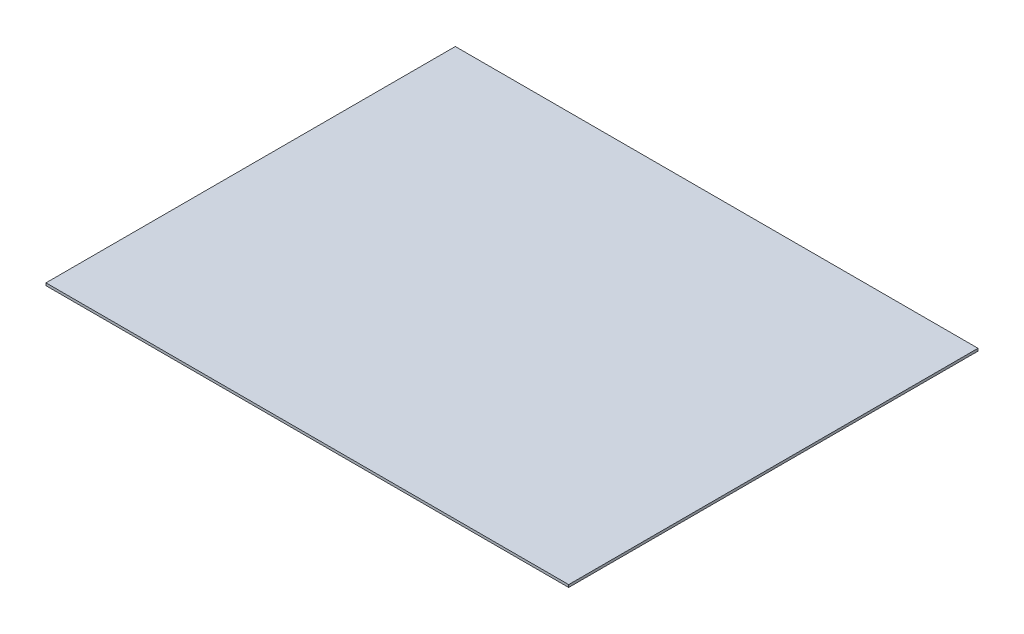
SolidWorks part; units mm, degrees
ref_plane "Front Plane" through (0, 0, 0) normal (0, 0, 1) x (1, 0, 0)
ref_plane "Top Plane" through (0, 0, 0) normal (0, 1, 0) x (1, 0, 0)
ref_plane "Right Plane" through (0, 0, 0) normal (1, 0, 0) x (0, 0, -1)
sketch "Sketch1" plane through (0, 0, 0) normal (0, 1, 0) x (1, 0, 0)
  line L1 (-124.5, 97.5) -> (124.5, 97.5)
  line L2 (-124.5, 97.5) -> (-124.5, -97.5)
  line L3 (-124.5, -97.5) -> (124.5, -97.5)
  line L4 (124.5, 97.5) -> (124.5, -97.5)
  line L5 (-124.5, 97.5) -> (124.5, -97.5) construction
  line L6 (-124.5, -97.5) -> (124.5, 97.5) construction
  point P0 (0, 0)
  dimension "D1" = 249
  dimension "D2" = 195
extrude "Boss-Extrude1" add sketch "Sketch1" along normal blind 1.2
